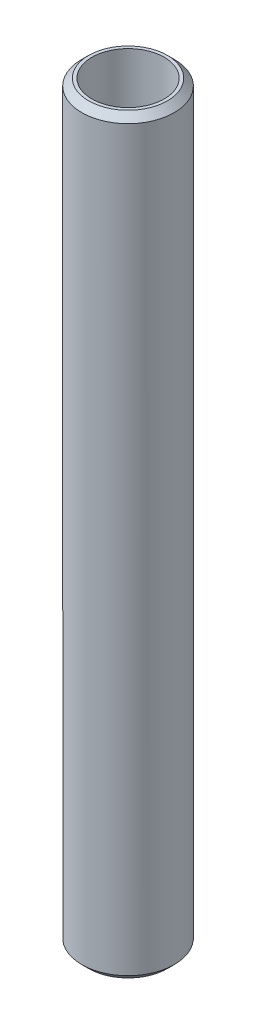
SolidWorks part; units mm, degrees
ref_plane "Front Plane" through (0, 0, 0) normal (0, 0, 1) x (1, 0, 0)
ref_plane "Top Plane" through (0, 0, 0) normal (0, 1, 0) x (1, 0, 0)
ref_plane "Right Plane" through (0, 0, 0) normal (1, 0, 0) x (0, 0, -1)
sketch "Sketch1" plane through (0, 0, 0) normal (0, 1, 0) x (1, 0, 0)
  circle A0 centre (0, 0) radius 22.5
  dimension "SHAFT_OD" = 45
extrude "Boss-Extrude1" add sketch "Sketch1" along normal blind 365.8815
sketch "Sketch2" plane through (0, 0, 0) normal (0, 1, 0) x (1, 0, 0)
  circle A0 centre (0, 0) radius 17.6109
  dimension "BORE_D" = 35.2218
extrude "Cut-Extrude1" cut sketch "Sketch2" along normal through all
chamfer "Chamfer1" distance 3.3235 angle 45 2 edges at (0, 365.8815, 22.5) (0, 0, 22.5)
